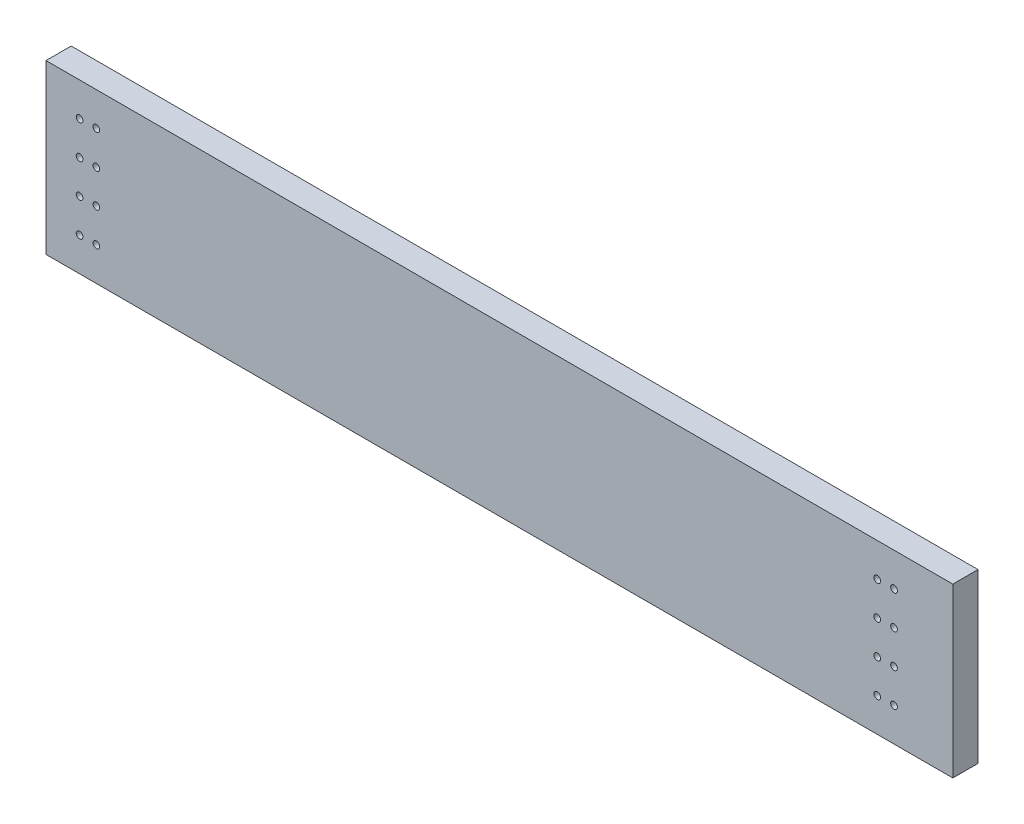
SolidWorks part; units mm, degrees
material "Pine"
ref_plane "Front Plane" through (0, 0, 0) normal (0, 0, 1) x (1, 0, 0)
ref_plane "Top Plane" through (0, 0, 0) normal (0, 1, 0) x (1, 0, 0)
ref_plane "Right Plane" through (0, 0, 0) normal (1, 0, 0) x (0, 0, -1)
sketch "Sketch1" plane through (0, 0, 0) normal (0, 0, 1) x (1, 0, 0)
  line L1 (-342.9, -63.5) -> (342.9, -63.5)
  line L2 (-342.9, -63.5) -> (-342.9, 63.5)
  line L3 (-342.9, 63.5) -> (342.9, 63.5)
  line L4 (342.9, -63.5) -> (342.9, 63.5)
  line L5 (-342.9, -63.5) -> (342.9, 63.5) construction
  line L6 (-342.9, 63.5) -> (342.9, -63.5) construction
  point P0 (0, 0)
  dimension "D1" = 685.8
  dimension "D2" = 127
extrude "Boss-Extrude1" add sketch "Sketch1" along normal blind 19.05
sketch "Sketch2" plane through (0, 0, 19.05) normal (0, 0, 1) x (1, 0, 0)
  line L0 (342.9, -63.5) -> (342.9, 63.5) construction
  line L1 (342.9, 63.5) -> (-342.9, 63.5) construction
  line L3 (-342.9, 63.5) -> (-342.9, -63.5) construction
  circle A1 centre (298.45, 38.1) radius 2.54
  circle A2 centre (298.45, 12.7) radius 2.54
  circle A3 centre (298.45, -12.7) radius 2.54
  circle A4 centre (298.45, -38.1) radius 2.54
  circle A5 centre (285.75, -38.1) radius 2.54
  circle A6 centre (285.75, -12.7) radius 2.54
  circle A7 centre (285.75, 12.7) radius 2.54
  circle A8 centre (285.75, 38.1) radius 2.54
  circle A9 centre (-317.5, 38.1) radius 2.54
  circle A10 centre (-304.8, 38.1) radius 2.54
  circle A11 centre (-317.5, 12.7) radius 2.54
  circle A12 centre (-304.8, 12.7) radius 2.54
  circle A13 centre (-317.5, -12.7) radius 2.54
  circle A14 centre (-304.8, -12.7) radius 2.54
  circle A15 centre (-317.5, -38.1) radius 2.54
  circle A16 centre (-304.8, -38.1) radius 2.54
  point P36 (0, 0)
  point P37 (0, 0)
  point P38 (0, 0)
  point P39 (0, 0)
  point P40 (0, 0)
  point P41 (0, 0)
  point P42 (0, 0)
  dimension "D1" = 5.08
  dimension "D8" = 5.08
  dimension "D2" = 44.45
  dimension "D3" = 12.7
  dimension "D4" = 25.4
  dimension "D5" = 25.4
  dimension "D6" = 25.4
  dimension "D7" = 25.4
  dimension "D9" = 25.4
  dimension "D10" = 25.4
  dimension "D11" = 25.4
  dimension "D12" = 25.4
  dimension "D13" = 25.4
  dimension "D14" = 12.7
extrude "Cut-Extrude1" cut sketch "Sketch2" against normal through all
